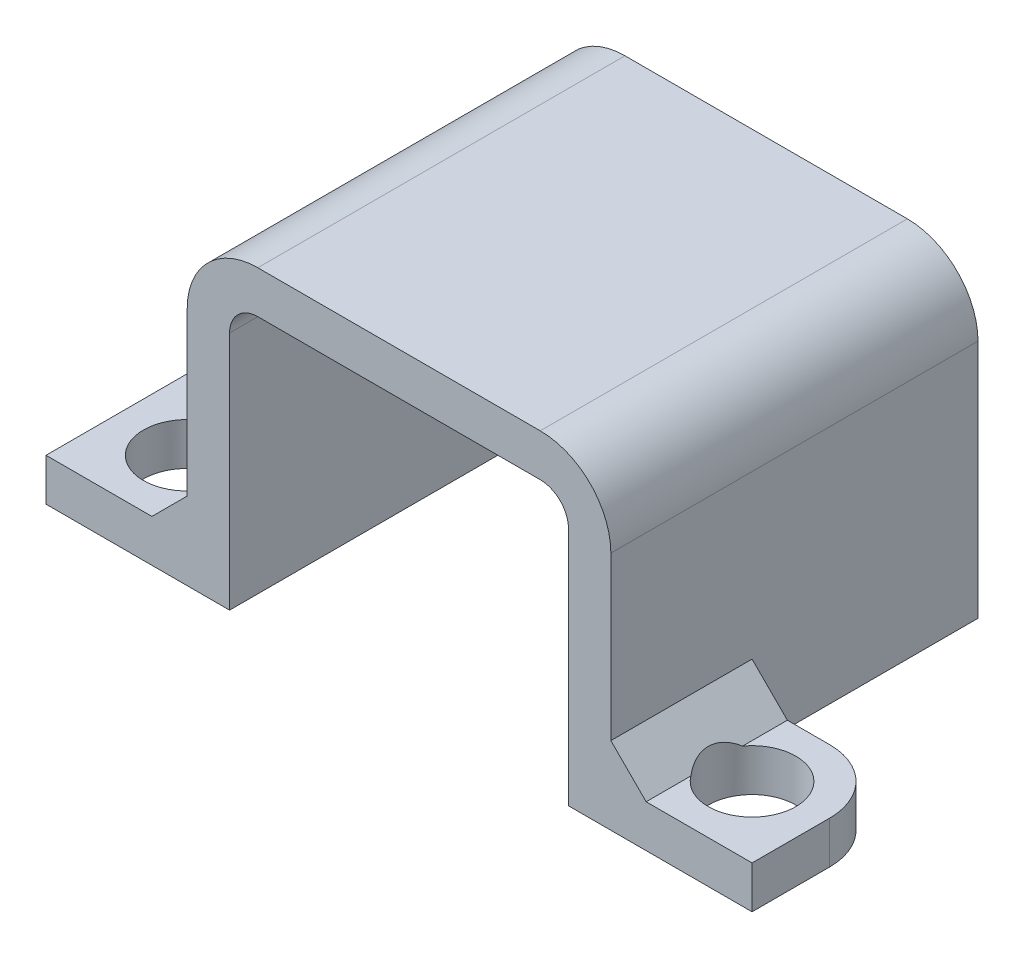
SolidWorks part; units mm, degrees
ref_plane "Front Plane" through (0, 0, 0) normal (0, 0, 1) x (1, 0, 0)
ref_plane "Top Plane" through (0, 0, 0) normal (0, 1, 0) x (1, 0, 0)
ref_plane "Right Plane" through (0, 0, 0) normal (1, 0, 0) x (0, 0, -1)
sketch "Sketch1" plane through (0, 0, 0) normal (0, 0, 1) x (1, 0, 0)
  line L0 (0, 1.5) -> (0, -9.7234) construction
  line L1 (6, 0) -> (-6, 0)
  line L2 (-6, 0) -> (-6, -9.5)
  line L3 (-6, -9.5) -> (-12.5, -9.5)
  line L4 (-12.5, -9.5) -> (-12.5, -8)
  line L5 (-12.5, -8) -> (-7.5, -8)
  line L6 (-7.5, -8) -> (-7.5, 1.5)
  line L7 (-7.5, 1.5) -> (7.5, 1.5)
  line L8 (12.5, -9.5) -> (12.5, -8)
  line L9 (12.5, -8) -> (7.5, -8)
  line L10 (6, -9.5) -> (12.5, -9.5)
  line L11 (6, 0) -> (6, -9.5)
  line L12 (7.5, -8) -> (7.5, 1.5)
  point P9 (-9.25, -9.5)
  point P17 (0, 0)
  dimension "D1" = 9.5
  dimension "D2" = 12
  dimension "D3" = 1.5
  dimension "D4" = 1.5
  dimension "D5" = 5
  dimension "D6" = 1.5
extrude "Boss-Extrude1" add sketch "Sketch1" against normal blind 13
sketch "Sketch2" plane through (0, -8, 0) normal (0, 1, 0) x (1, 0, 0)
  line L0 (7.5, 13) -> (7.5, 0) construction
  line L1 (12.5, 13) -> (7.5, 13)
  line L2 (12.5, 13) -> (12.5, 5)
  line L3 (12.5, 5) -> (7.5, 5)
  line L4 (7.5, 13) -> (7.5, 5)
  line L6 (12.5, 0) -> (7.5, 0) construction
  dimension "D1" = 5
extrude "Cut-Extrude1" cut sketch "Sketch2" against normal through all
sketch "Sketch3" plane through (0, -8, 0) normal (0, 1, 0) x (1, 0, 0)
  line L0 (12.5, 2.5) -> (-12.5, 2.5) construction
  line L1 (12.5, 5) -> (12.5, 0) construction
  line L2 (-12.5, 13) -> (-12.5, 0) construction
  line L3 (12.5, 5) -> (12.5, 0) construction
  line L4 (-7.5, 13) -> (-7.5, 0) construction
  circle A0 centre (10, 2.5) radius 1.55
  circle A1 centre (-10, 2.5) radius 1.55
  dimension "D1" = 3.1
  dimension "D2" = 2.5
  dimension "D3" = 3.1
  dimension "D4" = 2.5
extrude "Cut-Extrude2" cut sketch "Sketch3" against normal through all
fillet "Fillet1" radius 1 2 edges at (-6, 0, -6.5) (6, 0, -6.5)
fillet "Fillet2" radius 2.5 2 edges at (-7.5, 1.5, -6.5) (7.5, 1.5, -6.5)
chamfer "Chamfer1" distance 4 angle 45 1 edges at (-12.5, -8.75, -13)
fillet "Fillet3" radius 2.25 2 edges at (-12.5, -8.75, -9) (-8.5, -8.75, -13)
fillet "Fillet4" radius 2.25 1 edges at (12.5, -8.75, -5)
chamfer "Chamfer2" distance 1.25 angle 45 2 edges at (-7.5, -8, -6.5) (7.5, -8, -2.5)
